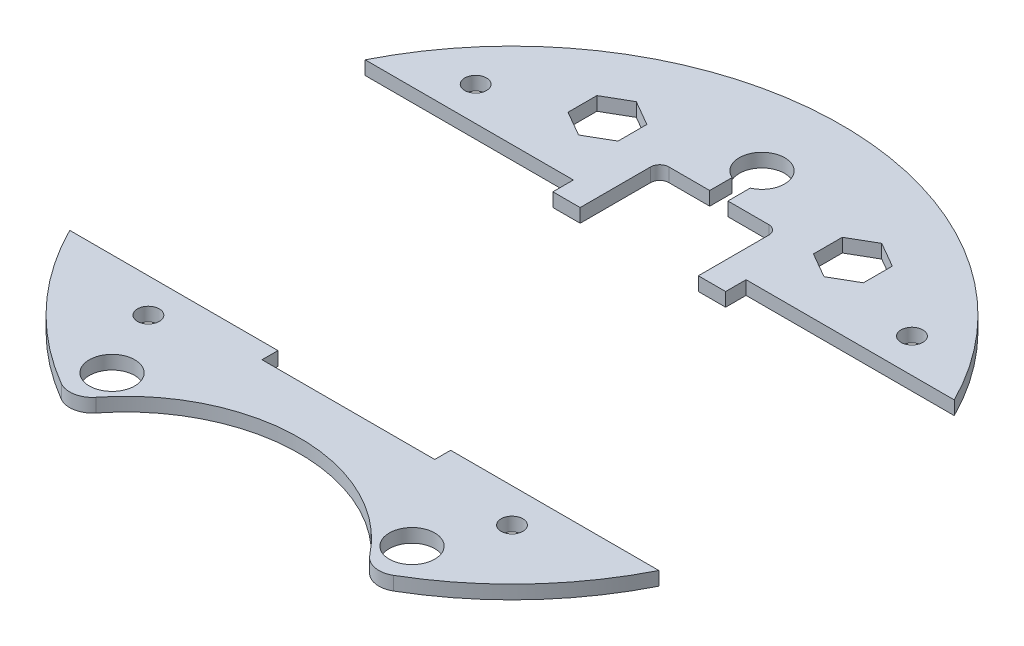
SolidWorks part; units mm, degrees
material "Acrylic (Medium-high impact)"
ref_plane "Front Plane" through (0, 0, 0) normal (0, 0, 1) x (1, 0, 0)
ref_plane "Top Plane" through (0, 0, 0) normal (0, 1, 0) x (1, 0, 0)
ref_plane "Right Plane" through (0, 0, 0) normal (1, 0, 0) x (0, 0, -1)
sketch "Sketch1" plane through (0, 0, 0) normal (0, 1, 0) x (1, 0, 0)
  line L0 (0, -85) -> (-32.4891, -64.8129) construction
  line L1 (0, -85) -> (0, 0) construction
  arc A0 (36.5434, -62.6165) -> (-36.5434, -62.6165) centre (0, 0) ccw
  arc A1 (30.0898, -61.3851) -> (-30.0898, -61.3851) centre (0, -85) ccw
  arc A2 (36.5434, -62.6165) -> (30.0898, -61.3851) centre (34.0231, -58.2982) cw
  arc A3 (-30.0898, -61.3851) -> (-36.5434, -62.6165) centre (-34.0231, -58.2982) cw
  dimension "D1" = 145
  dimension "D2" = 76.5
  dimension "D4" = 5
  dimension "D3" = 85
extrude "Boss-Extrude1" add sketch "Sketch1" along normal blind 3
sketch "solenoid placement" plane through (0, 3, 0) normal (0, 1, 0) x (1, 0, 0)
  line L4 (-19, -36) -> (19, -36)
  line L5 (-19, 28) -> (-19, -36)
  line L6 (19, 28) -> (-19, 28)
  line L7 (19, -36) -> (19, 28)
  line L8 (-19, -36) -> (19, -36)
  line L9 (-19, 28) -> (-19, -36)
  line L10 (19, 28) -> (-19, 28)
  line L11 (19, -36) -> (19, 28)
  dimension "D1" = 0
extrude "Cut-Extrude1" cut sketch "solenoid placement" against normal through all
sketch "Sketch5" plane through (0, 3, 0) normal (0, 1, 0) x (1, 0, 0)
  line L12 (-21.5, 51.1754) -> (-27, 54.3509)
  line L13 (-27, 54.3509) -> (-32.5, 51.1754)
  line L14 (-32.5, 51.1754) -> (-32.5, 44.8246)
  line L15 (-32.5, 44.8246) -> (-27, 41.6491)
  line L16 (-27, 41.6491) -> (-21.5, 44.8246)
  line L17 (-21.5, 44.8246) -> (-21.5, 51.1754)
  line L18 (-21.5, 51.1754) -> (-27, 54.3509)
  line L19 (-27, 54.3509) -> (-32.5, 51.1754)
  line L20 (-32.5, 51.1754) -> (-32.5, 44.8246)
  line L21 (-32.5, 44.8246) -> (-27, 41.6491)
  line L22 (-27, 41.6491) -> (-21.5, 44.8246)
  line L23 (-21.5, 44.8246) -> (-21.5, 51.1754)
  line L24 (21.5, 51.1754) -> (21.5, 44.8246)
  line L25 (21.5, 44.8246) -> (27, 41.6491)
  line L26 (27, 41.6491) -> (32.5, 44.8246)
  line L27 (32.5, 44.8246) -> (32.5, 51.1754)
  line L28 (32.5, 51.1754) -> (27, 54.3509)
  line L29 (27, 54.3509) -> (21.5, 51.1754)
  line L42 (21.5, 51.1754) -> (21.5, 44.8246)
  line L43 (21.5, 44.8246) -> (27, 41.6491)
  line L44 (27, 41.6491) -> (32.5, 44.8246)
  line L45 (32.5, 44.8246) -> (32.5, 51.1754)
  line L46 (32.5, 51.1754) -> (27, 54.3509)
  line L47 (27, 54.3509) -> (21.5, 51.1754)
  dimension "D1" = 0
  dimension "D2" = 0
extrude "Cut-Extrude5" cut sketch "Sketch5" against normal through all
sketch "Sketch6" plane through (0, 3, 0) normal (0, 1, 0) x (1, 0, 0)
  circle A0 centre (48, 40) radius 2.4
  circle A1 centre (40, -40) radius 2.4
  circle A2 centre (40, -40) radius 2.4 construction
  circle A3 centre (-40, -40) radius 2.4
  circle A4 centre (-40, -40) radius 2.4 construction
  circle A5 centre (48, 40) radius 2.4
  circle A6 centre (48, 40) radius 2.4 construction
  circle A7 centre (-48, 40) radius 2.4
  circle A8 centre (-48, 40) radius 2.4 construction
  circle A9 centre (-48, 40) radius 2.4
  circle A10 centre (40, -40) radius 2.4
  circle A11 centre (-40, -40) radius 2.4
  dimension "D5" = 4.8
extrude "Cut-Extrude6" cut sketch "Sketch6" against normal through all
sketch "Sketch3" plane through (0, 3, 0) normal (0, 1, 0) x (1, 0, 0)
  line L0 (-19, 28) -> (-19, 32.5)
  line L1 (72.5, -32.5) -> (-72.5, -32.5)
  line L2 (72.5, -32.5) -> (72.5, 32.5)
  line L3 (72.5, 32.5) -> (19, 32.5)
  line L4 (-72.5, -32.5) -> (-72.5, 32.5)
  line L5 (72.5, -32.5) -> (-72.5, 32.5) construction
  line L6 (72.5, 32.5) -> (-72.5, -32.5) construction
  line L7 (-19, 28) -> (19, 28)
  line L8 (19, 28) -> (19, 32.5)
  line L9 (-19, 32.5) -> (-72.5, 32.5)
  line L10 (-19, 28) -> (-19, -36) construction
  arc A0 (36.5434, -62.6165) -> (-36.5434, -62.6165) centre (0, 0) ccw construction
  point P0 (0, 0)
  dimension "D1" = 65
extrude "Cut-Extrude3" cut sketch "Sketch3" against normal through all
sketch "Sketch7" plane through (0, 3, 0) normal (0, 1, 0) x (1, 0, 0)
  line L8 (13, 28) -> (13, 43.5)
  line L9 (-13, 28) -> (13, 28)
  line L10 (-13, 43.5) -> (-13, 28)
  line L11 (11, 45.5) -> (-11, 45.5)
  line L28 (13, 28) -> (13, 43.5)
  line L29 (-13, 28) -> (13, 28)
  line L30 (-13, 43.5) -> (-13, 28)
  line L31 (11, 45.5) -> (-11, 45.5)
  arc A4 (-11, 45.5) -> (-13, 43.5) centre (-11, 43.5) ccw
  arc A5 (13, 43.5) -> (11, 45.5) centre (11, 43.5) ccw
  arc A14 (-11, 45.5) -> (-13, 43.5) centre (-11, 43.5) ccw
  arc A15 (13, 43.5) -> (11, 45.5) centre (11, 43.5) ccw
  dimension "D1" = 0
extrude "Cut-Extrude7" cut sketch "Sketch7" against normal through all
sketch "Sketch8" plane through (0, 3, 0) normal (0, 1, 0) x (1, 0, 0)
  line L0 (0, 0) -> (0, -21.9152) construction
  circle A1 centre (33, -55) radius 5
  circle A4 centre (-33, -55) radius 5
  dimension "D3" = 10
  dimension "D1" = 33
  dimension "D2" = 55
extrude "Cut-Extrude8" cut sketch "Sketch8" against normal through all
sketch "Sketch9" plane through (0, 3, 0) normal (0, 1, 0) x (1, 0, 0)
  line L0 (0, 0) -> (0, 55) construction
  line L1 (2, 0) -> (2, 50.4174)
  line L2 (-2, 0) -> (-2, 50.4174)
  line L3 (2, 0) -> (2, 55) construction
  line L4 (-2, 0) -> (-2, 55) construction
  arc A0 (2, 50.4174) -> (-2, 50.4174) centre (0, 55) ccw
  arc A1 (2, 0) -> (-2, 0) centre (0, 0) cw
  dimension "D1" = 10
  dimension "D2" = 55
  dimension "D3" = 2
  dimension "D4" = 2
extrude "Cut-Extrude9" cut sketch "Sketch9" against normal through all
equation "\"smallPulleyTeeth\"= 30"
equation "\"largePulleyTeeth\"= 30"
equation "\"eighthThick\"= 3.0mm"
equation "\"sixteenthThick\"= 1.7mm"
equation "\"quarterThick\"=6.0mm"
equation "\"OD\"= 145mm"
equation "\"puckAngle\"= 60.5deg"
equation "\"D1@Sketch1\"=\"OD\""
equation "\"puckDiam\"= 76.5mm"
equation "\"D2@Sketch1\"=\"puckDiam\""
equation "\"D1@Boss-Extrude1\"=\"eighthThick\""
equation "\"axlePress\"= 5.9mm"
equation "\"press\"= 0.2mm"
equation "\"wheelClear\"= 0.3mm"
equation "\"10-32clear\"= 4.8mm"
equation "\"6-32clear\"= 3.3mm"
equation "\"8-32clear\"= 4.0mm"
equation "\"wheelHeight\"= 22mm"
equation "\"wheelWell\"= 65mm"
equation "\"D1@Sketch3\"=\"wheelWell\""
equation "\"puckDist\"= 85mm"
equation "\"scoopFillet\"= 5mm"
equation "\"4-40clear\"= 3.0mm"
equation "\"D3@Sketch1\"=\"puckDist\""
equation "\"D4@Sketch1\"=\"scoopFillet\""
equation "\"10-32tap\"= 4.45mm"
equation "\"D5@Sketch6\"=\"10-32clear\""
